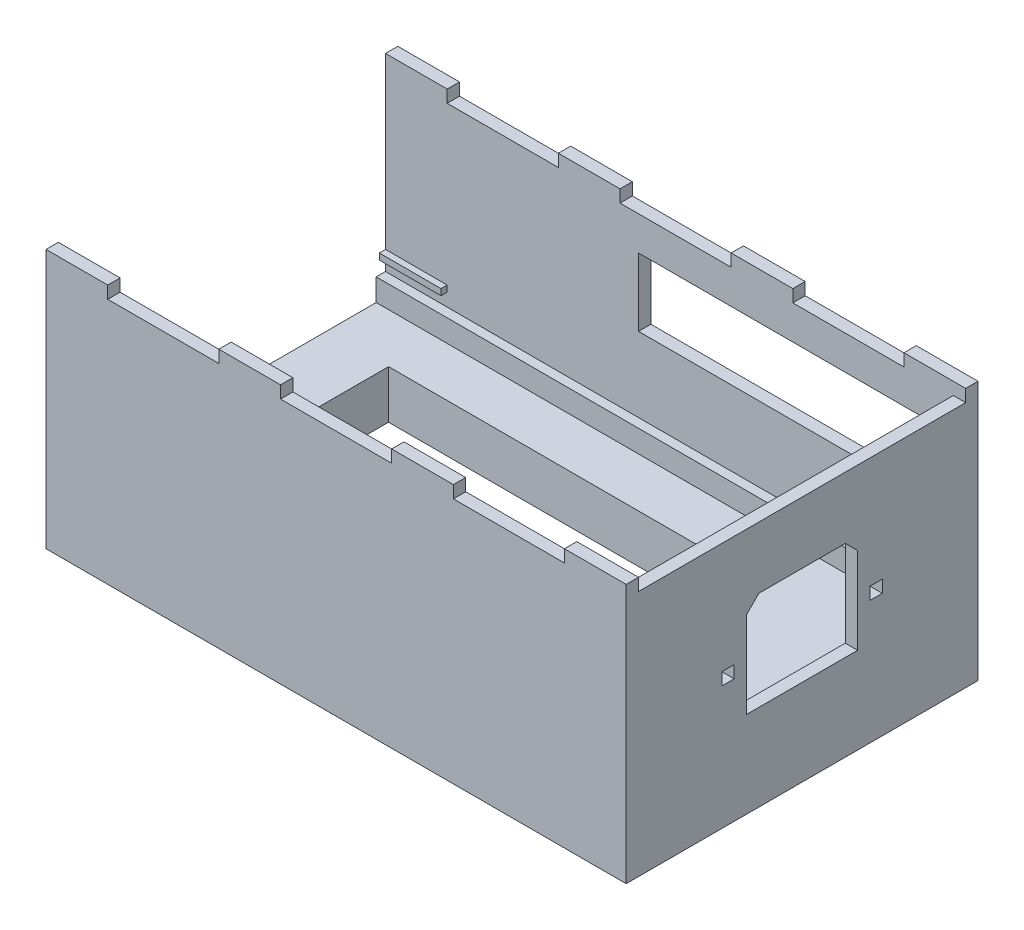
SolidWorks part; units mm, degrees
ref_plane "Front Plane" through (0, 0, 0) normal (0, 0, 1) x (1, 0, 0)
ref_plane "Top Plane" through (0, 0, 0) normal (0, 1, 0) x (1, 0, 0)
ref_plane "Right Plane" through (0, 0, 0) normal (1, 0, 0) x (0, 0, -1)
sketch "Sketch1" plane through (0, 0, 0) normal (0, 1, 0) x (1, 0, 0)
  line L1 (-30.298, 32.6459) -> (63.702, 32.6459)
  line L2 (-30.298, 32.6459) -> (-30.298, -24.3541)
  line L3 (-30.298, -24.3541) -> (63.702, -24.3541)
  line L4 (63.702, 32.6459) -> (63.702, -24.3541)
  dimension "D1" = 94
  dimension "D2" = 57
extrude "Boss-Extrude1" add sketch "Sketch1" along normal blind 10
sketch "Sketch2" plane through (0, 10, 0) normal (0, 1, 0) x (1, 0, 0)
  line L0 (-30.298, 32.6459) -> (63.702, 32.6459)
  line L1 (63.702, 32.6459) -> (63.702, -24.3541)
  line L2 (63.702, -24.3541) -> (-30.298, -24.3541)
  line L3 (-30.298, -24.3541) -> (-30.298, -22.3541)
  line L4 (-30.298, 32.6459) -> (-30.298, -24.3541) construction
  line L5 (-30.298, -22.3541) -> (61.702, -22.3541)
  line L6 (61.702, -22.3541) -> (61.702, 30.6459)
  line L7 (61.702, 30.6459) -> (-30.298, 30.6459)
  line L8 (-30.298, 30.6459) -> (-30.298, 32.6459)
  dimension "D1" = 2
  dimension "D2" = 2
  dimension "D3" = 2
extrude "Boss-Extrude2" add sketch "Sketch2" along normal blind 30
sketch "Sketch3" plane through (-30.298, 0, 0) normal (-1, 0, 0) x (0, 0, 1)
  line L0 (-30.6459, 40) -> (-30.6459, 10) construction
  line L1 (-30.6459, 10) -> (-29.1459, 10)
  line L2 (-30.6459, 10) -> (-30.6459, 11.4)
  line L3 (-30.6459, 11.4) -> (-29.1459, 11.4)
  line L4 (-29.1459, 10) -> (-29.1459, 11.4)
  line L5 (22.3541, 10) -> (20.8541, 10)
  line L6 (22.3541, 10) -> (22.3541, 11.4)
  line L7 (22.3541, 11.4) -> (20.8541, 11.4)
  line L8 (20.8541, 10) -> (20.8541, 11.4)
  line L9 (-30.6459, 14.5) -> (-29.6459, 14.5)
  line L10 (-30.6459, 14.5) -> (-30.6459, 13.5)
  line L11 (-30.6459, 13.5) -> (-29.6459, 13.5)
  line L12 (-29.6459, 14.5) -> (-29.6459, 13.5)
  line L13 (22.3541, 40) -> (22.3541, 10) construction
  line L14 (22.3541, 13.5) -> (21.3541, 13.5)
  line L15 (22.3541, 13.5) -> (22.3541, 14.5)
  line L16 (22.3541, 14.5) -> (21.3541, 14.5)
  line L17 (21.3541, 13.5) -> (21.3541, 14.5)
  dimension "D1" = 1.5
  dimension "D2" = 1.4
  dimension "D3" = 1.5
  dimension "D4" = 1.4
  dimension "D5" = 2.1
  dimension "D6" = 2.1
  dimension "D8" = 1
  dimension "D9" = 1
  dimension "D10" = 1
  dimension "D11" = 1
extrude "Boss-Extrude3" add sketch "Sketch3" against normal up to surface (92 mm away) contours L1 L4 L3 L2 | L5 L8 L7 L6 | L17 L16 L15 L14 up to face at (61.702, 25, -4.1459)
extrude "Boss-Extrude4" add sketch "Sketch3<3>" against normal blind 10 contours L12 L11 L10 L9
sketch "Sketch3<3>" plane through (-30.298, 0, 0) normal (-1, 0, 0) x (0, 0, 1) same geometry as "Sketch3"
sketch "Sketch4" plane through (0, 0, -32.6459) normal (0, 0, -1) x (-1, 0, 0)
  line L0 (-63.702, 40) -> (-63.702, 0) construction
  line L1 (-56.702, 34.5) -> (-10.702, 34.5)
  line L2 (-56.702, 34.5) -> (-56.702, 23.5)
  line L3 (-56.702, 23.5) -> (-10.702, 23.5)
  line L4 (-10.702, 34.5) -> (-10.702, 23.5)
  point P4 (-56.702, 29)
  dimension "D1" = 7
  dimension "D2" = 46
  dimension "D3" = 11
  dimension "D4" = 9
extrude "Cut-Extrude1" cut sketch "Sketch4" against normal blind 10
sketch "Sketch5" plane through (63.702, 0, 0) normal (1, 0, 0) x (0, 0, -1)
  line L0 (-4.8541, 21) -> (13.1459, 21) construction
  line L1 (-2.8541, 30) -> (11.1459, 30)
  line L2 (-4.8541, 28) -> (-4.8541, 14)
  line L3 (-4.8541, 14) -> (13.1459, 14)
  line L4 (13.1459, 28) -> (13.1459, 14)
  line L5 (-24.3541, 40) -> (32.6459, 40) construction
  line L6 (4.1459, 40) -> (4.1459, 0) construction
  line L7 (-4.8541, 21) -> (-24.3541, 21) construction
  line L8 (-24.3541, 0) -> (32.6459, 0) construction
  line L9 (-24.3541, 40) -> (-24.3541, 0) construction
  line L10 (13.1459, 21) -> (32.6459, 21) construction
  line L11 (32.6459, 40) -> (32.6459, 0) construction
  line L12 (11.1459, 30) -> (13.1459, 28)
  line L13 (-8.8541, 22) -> (-6.8541, 22)
  line L14 (-8.8541, 22) -> (-8.8541, 20)
  line L15 (-8.8541, 20) -> (-6.8541, 20)
  line L16 (-6.8541, 22) -> (-6.8541, 20)
  line L17 (15.1459, 22) -> (17.1459, 22)
  line L18 (15.1459, 22) -> (15.1459, 20)
  line L19 (15.1459, 20) -> (17.1459, 20)
  line L20 (17.1459, 22) -> (17.1459, 20)
  line L21 (-4.8541, 28) -> (-2.8541, 30)
  point P10 (4.1459, 30)
  point P27 (-6.8541, 21)
  point P28 (17.1459, 21)
  dimension "D1" = 0
  dimension "D3" = 10
  dimension "D5" = 2
  dimension "D6" = 0
  dimension "D7" = 2
  dimension "D8" = 2
  dimension "D9" = 2
  dimension "D10" = 2
  dimension "D11" = 0
  dimension "D12" = 2
  dimension "D13" = 45
  dimension "D15" = 45
extrude "Cut-Extrude2" cut sketch "Sketch5" against normal up to surface (2 mm away) up to face at (61.702, 16.8, 4.5207)
ref_plane "Plane5" through (0, 33, 0) normal (0, 1, 0) x (1, 0, 0)
sketch "Sketch7" plane through (0, 33, 0) normal (0, 1, 0) x (1, 0, 0)
  line L0 (61.702, -22.3541) -> (-30.298, -22.3541) construction
  line L1 (10.702, -22.3541) -> (61.702, -22.3541)
  line L2 (10.702, -22.3541) -> (10.702, -20.3541)
  line L3 (10.702, -20.3541) -> (59.702, -20.3541)
  line L4 (61.702, -22.3541) -> (61.702, -20.3541)
  line L5 (61.702, 29.1459) -> (61.702, -20.8541) construction
  line L6 (61.702, 30.6459) -> (61.702, -22.3541) construction
  line L8 (59.702, -20.3541) -> (59.702, 15.6459)
  line L9 (59.702, 15.6459) -> (61.702, 15.6459)
  line L10 (61.702, -20.3541) -> (61.702, 15.6459)
  dimension "D1" = 51
  dimension "D2" = 2
  dimension "D3" = 38
  dimension "D4" = 2
extrude "Boss-Extrude5" add sketch "Sketch7" against normal blind 2 contours L3 L8 L9 L10 L4 L1 L2
fillet "Fillet1" radius 1.5 2 edges at (59.702, 31, 2.3541) (35.202, 31, 20.3541) conic radius 3
ref_plane "Plane6" through (0, 34.8, 0) normal (0, 1, 0) x (1, 0, 0)
sketch "Sketch8" plane through (0, 34.8, 0) normal (0, 1, 0) x (1, 0, 0)
  line L1 (10.702, -20.3541) -> (59.702, -20.3541)
  line L2 (10.702, -20.3541) -> (10.702, -22.3541)
  line L3 (10.702, -22.3541) -> (61.702, -22.3541)
  line L4 (61.702, -20.3541) -> (61.702, -22.3541)
  line L5 (61.702, -22.3541) -> (59.702, -22.3541)
  line L6 (61.702, -22.3541) -> (61.702, 15.6459)
  line L7 (61.702, 15.6459) -> (59.702, 15.6459)
  line L8 (59.702, -20.3541) -> (59.702, 15.6459)
extrude "Boss-Extrude6" add sketch "Sketch8" along normal blind 1 contours L6 L7 L8 L1 L2 L3
sketch "Sketch9" plane through (0, 40, 0) normal (0, 1, 0) x (1, 0, 0)
  line L0 (-30.298, 30.6459) -> (61.702, 30.6459) construction
  line L1 (-30.298, 32.6459) -> (-20.298, 32.6459)
  line L2 (-30.298, 32.6459) -> (-30.298, 30.6459)
  line L3 (-30.298, 30.6459) -> (-20.298, 30.6459)
  line L4 (-20.298, 32.6459) -> (-20.298, 30.6459)
  line L5 (61.702, 30.6459) -> (-30.298, 30.6459) construction
  line L6 (-2.298, 30.6459) -> (7.702, 30.6459)
  line L7 (-2.298, 30.6459) -> (-2.298, 32.6459)
  line L8 (-2.298, 32.6459) -> (7.702, 32.6459)
  line L9 (7.702, 30.6459) -> (7.702, 32.6459)
  line L10 (63.702, 32.6459) -> (-30.298, 32.6459) construction
  line L11 (61.702, -22.3541) -> (-30.298, -22.3541) construction
  line L12 (25.702, 30.6459) -> (35.702, 30.6459)
  line L13 (25.702, 30.6459) -> (25.702, 32.6459)
  line L14 (25.702, 32.6459) -> (35.702, 32.6459)
  line L15 (35.702, 30.6459) -> (35.702, 32.6459)
  line L16 (53.702, 30.6459) -> (63.702, 30.6459)
  line L17 (53.702, 30.6459) -> (53.702, 32.6459)
  line L18 (53.702, 32.6459) -> (63.702, 32.6459)
  line L19 (63.702, 30.6459) -> (63.702, 32.6459)
  line L20 (-30.298, -24.3541) -> (-20.298, -24.3541)
  line L21 (-30.298, -24.3541) -> (-30.298, -22.3541)
  line L22 (-30.298, -22.3541) -> (-20.298, -22.3541)
  line L23 (-20.298, -24.3541) -> (-20.298, -22.3541)
  line L24 (-30.298, -24.3541) -> (63.702, -24.3541) construction
  line L25 (-2.298, -24.3541) -> (7.702, -24.3541)
  line L26 (-2.298, -24.3541) -> (-2.298, -22.3541)
  line L27 (-2.298, -22.3541) -> (7.702, -22.3541)
  line L28 (7.702, -24.3541) -> (7.702, -22.3541)
  line L29 (10.702, -22.3541) -> (61.702, -22.3541) construction
  line L30 (25.702, -24.3541) -> (35.702, -24.3541)
  line L31 (25.702, -24.3541) -> (25.702, -22.3541)
  line L32 (25.702, -22.3541) -> (35.702, -22.3541)
  line L33 (35.702, -24.3541) -> (35.702, -22.3541)
  line L35 (63.702, -24.3541) -> (53.702, -24.3541)
  line L36 (63.702, -24.3541) -> (63.702, -22.3541)
  line L37 (63.702, -22.3541) -> (53.702, -22.3541)
  line L38 (53.702, -24.3541) -> (53.702, -22.3541)
  dimension "D1" = 10
  dimension "D2" = 10
  dimension "D3" = 18
  dimension "D4" = 18
  dimension "D5" = 10
  dimension "D6" = 18
  dimension "D7" = 18
  dimension "D8" = 18
  dimension "D9" = 18
  dimension "D10" = 10
  dimension "D11" = 10
  dimension "D12" = 10
extrude "Boss-Extrude7" add sketch "Sketch9" along normal blind 2
sketch "Sketch10" plane through (0, 10, 0) normal (0, 1, 0) x (1, 0, 0)
  line L0 (-30.298, 4.1459) -> (61.702, 4.1459) construction
  line L1 (-20.298, 21.1459) -> (31.702, 21.1459)
  line L2 (-20.298, 21.1459) -> (-20.298, -12.8541)
  line L3 (-20.298, -12.8541) -> (31.702, -12.8541)
  line L4 (31.702, 21.1459) -> (31.702, -12.8541)
  line L5 (-30.298, 29.1459) -> (-30.298, -20.8541) construction
  line L6 (61.702, 30.6459) -> (61.702, -22.3541) construction
  point P10 (31.702, 4.1459)
  dimension "D1" = 34
  dimension "D2" = 0
  dimension "D3" = 52
  dimension "D4" = 10
extrude "Cut-Extrude3" cut sketch "Sketch10" against normal through all and the other way through all
sketch "Sketch11" plane through (0, 10, 0) normal (0, 1, 0) x (1, 0, 0)
  line L1 (61.702, 29.1459) -> (-30.298, 29.1459)
  line L2 (61.702, 29.1459) -> (61.702, -20.8541)
  line L3 (61.702, -20.8541) -> (-30.298, -20.8541)
  line L4 (-30.298, 29.1459) -> (-30.298, -20.8541)
extrude "Cut-Extrude4" cut sketch "Sketch11" against normal blind 2.2
